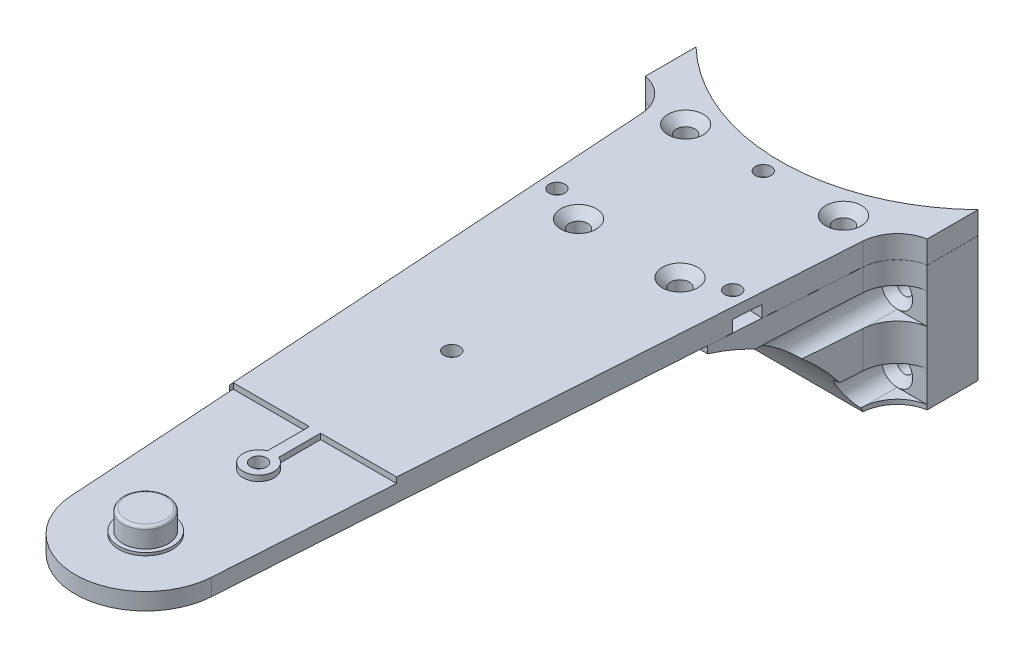
SolidWorks part; units mm, degrees
ref_plane "Front Plane" through (0, 0, 0) normal (0, 0, 1) x (1, 0, 0)
ref_plane "Top Plane" through (0, 0, 0) normal (0, 1, 0) x (1, 0, 0)
ref_plane "Right Plane" through (0, 0, 0) normal (1, 0, 0) x (0, 0, -1)
sketch "Sketch1" plane through (0, 0, 0) normal (0, 1, 0) x (1, 0, 0)
  line L0 (0, 0) -> (0, -148.5) construction
  line L1 (-22.202, -1.4609) -> (-12.473, -149.3207) construction
  line L2 (22.202, -1.4609) -> (12.473, -149.3207) construction
  line L3 (-12.473, -149.3207) -> (-19.6067, -40.9037)
  line L4 (12.473, -149.3207) -> (19.6067, -40.9037)
  line L5 (-25, -25.9037) -> (25, -25.9037) construction
  line L6 (-25, -25.9037) -> (-25, -34.9037)
  line L7 (25, -25.9037) -> (25, -34.9037)
  circle A0 centre (0, 0) radius 36 construction
  arc A1 (-12.473, -149.3207) -> (12.473, -149.3207) centre (0, -148.5) ccw
  circle A2 centre (0, 0) radius 19.5 construction
  circle A3 centre (0, 19.5) radius 2.75 construction
  circle A4 centre (0, 0) radius 22.25 construction
  arc A5 (-25, -25.9037) -> (25, -25.9037) centre (0, 0) ccw
  arc A6 (-25, -34.9037) -> (-19.6067, -40.9037) centre (-26.1174, -41.3321) cw
  arc A7 (25, -34.9037) -> (19.6067, -40.9037) centre (26.1174, -41.3321) ccw
  dimension "D1" = 72
  dimension "D3" = 25
  dimension "D4" = 39
  dimension "D5" = 5.5
  dimension "D2" = 148.5
  dimension "D6" = 50
  dimension "D7" = 9
  dimension "D8" = 15
extrude "Boss-Extrude1" add sketch "Sketch1" against normal blind 4
sketch "Sketch2" plane through (0, -4, 0) normal (0, -1, 0) x (1, 0, 0)
  line L0 (25, 34.9037) -> (25, 25.9037) construction
  line L1 (-25, 25.9037) -> (-25, 34.9037) construction
  line L2 (25, 34.9037) -> (25, 25.9037)
  line L3 (-25, 25.9037) -> (-25, 34.9037)
  line L4 (-19.6067, 40.9037) -> (19.6067, 40.9037)
  arc A0 (19.6067, 40.9037) -> (25, 34.9037) centre (26.1174, 41.3321) ccw construction
  arc A1 (25, 25.9037) -> (-25, 25.9037) centre (0, 0) ccw construction
  arc A2 (-25, 34.9037) -> (-19.6067, 40.9037) centre (-26.1174, 41.3321) ccw construction
  arc A3 (19.6067, 40.9037) -> (25, 34.9037) centre (26.1174, 41.3321) ccw
  arc A4 (25, 25.9037) -> (-25, 25.9037) centre (0, 0) ccw
  arc A5 (-25, 34.9037) -> (-19.6067, 40.9037) centre (-26.1174, 41.3321) ccw
extrude "Boss-Extrude2" add sketch "Sketch2" along normal offset from surface (22.2378 mm away) 26.2378 up to face at (0, 0, 65.2465)
ref_plane "Plane1" through (0, 0, 34.9037) normal (0, 0, 1) x (1, 0, 0)
fillet "Fillet2" radius 40 1 edges at (0, -4, 40.9037)
sketch "Sketch3" plane through (0, 0, 34.9037) normal (0, 0, 1) x (1, 0, 0)
  line L0 (25, 0) -> (-25, 0) construction
  line L1 (-19.6636, -22.6878) -> (19.6636, -22.6878) construction
  line L2 (-19.6636, -22.6878) -> (-19.6636, -10.6878) construction
  line L3 (-19.6636, -10.6878) -> (19.6636, -10.6878) construction
  line L4 (19.6636, -22.6878) -> (19.6636, -10.6878) construction
  line L5 (-19.6636, -22.6878) -> (19.6636, -10.6878) construction
  line L6 (-19.6636, -10.6878) -> (19.6636, -22.6878) construction
  line L7 (-19.6636, -7.9378) -> (-25, -7.9378)
  line L8 (-25, -7.9378) -> (-25, -13.4378)
  line L9 (-25, -13.4378) -> (-19.6636, -13.4378)
  line L10 (-25, -26.2378) -> (-25, 0) construction
  line L11 (0, -16.6878) -> (-25, -16.6878) construction
  line L12 (-25, -25.4378) -> (-25, -19.9378)
  line L13 (-25, -19.9378) -> (-19.6636, -19.9378)
  line L14 (-19.6636, -25.4378) -> (-25, -25.4378)
  line L15 (0, -16.6878) -> (0, 0) construction
  line L16 (19.6636, -25.4378) -> (25, -25.4378)
  line L17 (25, -19.9378) -> (19.6636, -19.9378)
  line L18 (25, -25.4378) -> (25, -19.9378)
  line L19 (25, -13.4378) -> (19.6636, -13.4378)
  line L20 (25, -7.9378) -> (25, -13.4378)
  line L21 (19.6636, -7.9378) -> (25, -7.9378)
  arc A0 (-19.6636, -13.4378) -> (-19.6636, -7.9378) centre (-19.6636, -10.6878) ccw
  arc A4 (-19.6636, -19.9378) -> (-19.6636, -25.4378) centre (-19.6636, -22.6878) cw
  arc A5 (19.6636, -19.9378) -> (19.6636, -25.4378) centre (19.6636, -22.6878) ccw
  arc A6 (19.6636, -13.4378) -> (19.6636, -7.9378) centre (19.6636, -10.6878) cw
  point P0 (0, -16.6878)
  dimension "D4" = 5.5
  dimension "D1" = 10.6878
  dimension "D2" = 12
  dimension "D3" = 39.3272
extrude "Cut-Extrude1" cut sketch "Sketch3" along normal through all
chamfer "Chamfer1" [suppressed] distance 2.75 angle 60
hole_wizard "CSK for M2.5 Flat Head Machine Screw1" positions "Sketch5" profile "Sketch6" countersink size "M2.5" standard "ANSI Metric" end condition through all
sketch "Sketch5" plane through (0, 0, 34.9037) normal (0, 0, 1) x (1, 0, 0)
  point P0 (19.6636, -22.6878)
  point P3 (-19.6636, -22.6878)
  point P6 (-19.6636, -10.6878)
  point P9 (19.6636, -10.6878)
sketch "Sketch6" plane through (19.6636, -22.6878, 34.9037) normal (1, 0, 0) x (0, -1, 0)
  line L0 (0, 0) -> (0, 9)
  line L1 (0, 9) -> (1.4, 9)
  line L2 (1.4, 9) -> (1.4, 1.35)
  line L3 (1.4, 1.35) -> (2.75, 0)
  line L5 (2.75, 0) -> (0, 0)
  line L6 (-1.4, 1.35) -> (-2.75, 0) construction
  line L11 (0, -6.35) -> (0, 107.95) construction
  dimension "Thru Hole Dia." = 2.8
  dimension "Thru Hole Depth" = 9
  dimension "Near C'Sink Dia." = 5.5
  dimension "Near C'Sink Angle" = 90
sketch "Sketch8" plane through (0, 0, 0) normal (0, 1, 0) x (1, 0, 0)
  line L9 (-3.9772, -124.3701) -> (-3.9783, -118.5007)
  line L10 (-3.9783, -118.5007) -> (-12.9545, -118.5024)
  line L11 (-12.9545, -118.5024) -> (-14.4578, -118.5026)
  line L12 (-14.4578, -118.5026) -> (-14.4468, -178.5026)
  line L13 (-14.4468, -178.5026) -> (14.5121, -178.4973)
  line L14 (14.5121, -178.4973) -> (14.5012, -118.4973)
  line L15 (14.5012, -118.4973) -> (12.9979, -118.4976)
  line L16 (12.9979, -118.4976) -> (4.0217, -118.4993)
  line L17 (4.0217, -118.4993) -> (4.0228, -124.3686)
  line L21 (-14.4578, -118.5026) -> (-14.4468, -178.5026)
  line L22 (-14.4468, -178.5026) -> (14.5121, -178.4973)
  line L23 (14.5121, -178.4973) -> (14.5012, -118.4973)
  line L27 (-0.9823, -96.8119) -> (-0.9769, -125.9384) construction
  line L28 (1.0177, -96.8116) -> (1.0231, -125.9381) construction
  line L29 (-0.9783, -118.5002) -> (-0.9769, -125.9384)
  line L30 (1.0217, -118.4998) -> (1.0231, -125.9381)
  line L31 (1.0217, -118.4998) -> (14.5012, -118.4973)
  line L72 (-14.4578, -118.5026) -> (-0.9783, -118.5002)
  arc A1 (-3.9772, -124.3701) -> (4.0228, -124.3686) centre (0.0235, -128.5) ccw
  arc A2 (-3.9772, -124.3701) -> (4.0228, -124.3686) centre (0.0235, -128.5) ccw construction
  arc A8 (-0.9769, -125.9384) -> (1.0231, -125.9381) centre (0.0235, -128.5) ccw
  dimension "D2" = 5.5
  dimension "D1" = 0
extrude "Cut-Extrude3" cut sketch "Sketch8" against normal blind 1
sketch "Sketch9" plane through (0, -4, 0) normal (0, -1, 0) x (1, 0, 0)
  line L0 (-17.2485, 76.7436) -> (17.2485, 76.7436)
  line L1 (17.2485, 76.7436) -> (17.9065, 66.7436)
  line L2 (17.9065, 66.7436) -> (-17.9065, 66.7436)
  line L3 (-17.9065, 66.7436) -> (-17.2485, 76.7436)
  line L4 (-17.2485, 76.7436) -> (-12.473, 149.3207) construction
  line L5 (12.473, 149.3207) -> (17.2485, 76.7436) construction
  dimension "D1" = 10
extrude "Cut-Extrude4" cut sketch "Sketch9" along normal through all
sketch "Sketch11" plane through (0, -4, 0) normal (0, -1, 0) x (1, 0, 0)
  circle A0 centre (0, 0) radius 161
extrude "Cut-Extrude5" cut sketch "Sketch11" along normal blind 0.01
sketch "Sketch12" plane through (0, 0, 0) normal (0, 1, 0) x (1, 0, 0)
  line L0 (-17.9065, -66.7436) -> (17.9065, -66.7436) construction
  line L1 (-17.9065, -66.7436) -> (17.9065, -66.7436) construction
  line L3 (-9, -62.7436) -> (9, -62.7436) construction
  line L4 (-9, -62.7436) -> (-14, -38.7436) construction
  line L5 (-14, -38.7436) -> (14, -38.7436) construction
  line L6 (9, -62.7436) -> (14, -38.7436) construction
  line L7 (-9, -62.7436) -> (14, -38.7436) construction
  line L8 (-14, -38.7436) -> (9, -62.7436) construction
  circle A0 centre (-14, -38.7436) radius 1.65
  circle A1 centre (14, -38.7436) radius 1.65
  circle A2 centre (-9, -62.7436) radius 1.65
  circle A3 centre (9, -62.7436) radius 1.65
  point P2 (0, -53.3523)
  point P15 (0, -62.7436)
  dimension "D1" = 3.3
  dimension "D2" = 4
  dimension "D3" = 28
  dimension "D4" = 24
  dimension "D5" = 18
extrude "Cut-Extrude6" cut sketch "Sketch12" against normal blind 8.25
ref_plane "Plane2" through (0, -5.2702, 0) normal (0, 1, 0) x (1, 0, 0)
sketch "Sketch13" plane through (0, -5.2702, 0) normal (0, 1, 0) x (1, 0, 0)
  line L0 (0, 0) -> (0, -36) construction
  line L1 (-11.75, -59.9936) -> (-6.25, -59.9936)
  line L2 (-11.75, -59.9936) -> (-11.75, -65.4936)
  line L3 (-11.75, -65.4936) -> (-6.25, -65.4936) construction
  line L4 (-6.25, -59.9936) -> (-6.25, -65.4936)
  line L5 (-11.75, -59.9936) -> (-6.25, -65.4936) construction
  line L6 (-11.75, -65.4936) -> (-6.25, -59.9936) construction
  line L7 (-6.25, -65.4936) -> (-6.25, -66.7436)
  line L8 (-17.9065, -66.7436) -> (17.9065, -66.7436) construction
  line L9 (-6.25, -66.7436) -> (-11.75, -66.7436)
  line L10 (-11.75, -66.7436) -> (-11.75, -65.4936)
  line L11 (6.25, -66.7436) -> (11.75, -66.7436)
  line L12 (6.25, -65.4936) -> (6.25, -66.7436)
  line L13 (6.25, -59.9936) -> (6.25, -65.4936)
  line L14 (11.75, -59.9936) -> (6.25, -59.9936)
  line L15 (11.75, -59.9936) -> (11.75, -65.4936)
  line L16 (11.75, -66.7436) -> (11.75, -65.4936)
  arc A0 (-25, -25.9037) -> (25, -25.9037) centre (0, 0) ccw construction
  point P0 (-9, -62.7436)
  dimension "D1" = 5.5
extrude "Cut-Extrude7" cut sketch "Sketch13" against normal blind 8.5
sketch "Sketch14" plane through (0, -8.25, 0) normal (0, 1, 0) x (1, 0, 0)
  line L0 (0, 0) -> (0, -36) construction
  line L1 (-14, -38.7436) -> (0, 0) construction
  line L2 (-15.6518, -35.2228) -> (-10.4791, -37.0919) construction
  line L3 (-15.6518, -35.2228) -> (-17.5209, -40.3954)
  line L4 (-17.5209, -40.3954) -> (-12.3482, -42.2645)
  line L5 (-10.4791, -37.0919) -> (-12.3482, -42.2645)
  line L6 (-15.6518, -35.2228) -> (-12.3482, -42.2645) construction
  line L7 (-17.5209, -40.3954) -> (-10.4791, -37.0919) construction
  line L8 (-15.6518, -35.2228) -> (-14.7849, -32.8239)
  line L9 (-14.7849, -32.8239) -> (-9.6123, -34.693)
  line L10 (-9.6123, -34.693) -> (-10.4791, -37.0919)
  line L11 (14.7849, -32.8239) -> (9.6123, -34.693)
  line L12 (15.6518, -35.2228) -> (14.7849, -32.8239)
  line L13 (15.6518, -35.2228) -> (17.5209, -40.3954)
  line L14 (17.5209, -40.3954) -> (12.3482, -42.2645)
  line L15 (10.4791, -37.0919) -> (12.3482, -42.2645)
  line L16 (9.6123, -34.693) -> (10.4791, -37.0919)
  arc A0 (-25, -25.9037) -> (25, -25.9037) centre (0, 0) ccw construction
  point P6 (-14, -38.7436)
  dimension "D1" = 5.5
extrude "Cut-Extrude8" cut sketch "Sketch14" along normal blind 2
hole_wizard "CSK for M3 Flat Head Machine Screw1" positions "Sketch15" profile "Sketch16" countersink size "M3" standard "ANSI Metric"
sketch "Sketch15" plane through (0, 0, 0) normal (0, 1, 0) x (1, 0, 0)
  point P0 (-14, -38.7436)
  point P3 (14, -38.7436)
  point P6 (9, -62.7436)
  point P9 (-9, -62.7436)
sketch "Sketch16" plane through (-14, 0, 38.7436) normal (1, 0, 0) x (0, 0, 1)
  line L0 (0, 0) -> (0, 8.9914)
  line L1 (0, 8.9914) -> (1.65, 8)
  line L2 (1.65, 8) -> (1.65, 1.5)
  line L3 (1.65, 1.5) -> (3.15, 0)
  line L5 (3.15, 0) -> (0, 0)
  line L6 (-1.65, 1.5) -> (-3.15, 0) construction
  line L10 (0, 8.9914) -> (-1.65, 8) construction
  line L11 (0, -6.35) -> (0, 107.95) construction
  dimension "Hole Dia." = 3.3
  dimension "Hole Depth" = 8
  dimension "Near C'Sink Dia." = 6.3
  dimension "Near C'Sink Angle" = 90
  dimension "Drill Angle" = 118
sketch "Sketch18" plane through (0, -4, 0) normal (0, -1, 0) x (1, 0, 0)
  circle A0 centre (0.0235, 128.5) radius 1.4
  circle A1 centre (0.0071, 39) radius 2.75
  circle A2 centre (0.0071, 39) radius 2.75 construction
  circle A3 centre (0.0173, 94.25) radius 2.75
  circle A4 centre (0.0173, 94.25) radius 2.75 construction
  circle A5 centre (0.0235, 128.5) radius 2.75
  circle A6 centre (0.0235, 128.5) radius 2.75 construction
  circle A7 centre (0.0173, 94.25) radius 1.4
  circle A9 centre (-15.5725, 60.0029) radius 1.4
  circle A11 centre (-15.5725, 60.0029) radius 2.75
  circle A12 centre (-15.5725, 60.0029) radius 2.75 construction
  circle A13 centre (15.5944, 59.9971) radius 1.4
  circle A15 centre (0.0071, 39) radius 1.4
  circle A17 centre (15.5944, 59.9971) radius 2.75
  circle A18 centre (15.5944, 59.9971) radius 2.75 construction
  dimension "D4" = 2.8
  dimension "D1" = 0
  dimension "D2" = 0
  dimension "D3" = 0
  dimension "D6" = 0
  dimension "D9" = 0
extrude "Cut-Extrude9" cut sketch "Sketch18" against normal through all
sketch "Sketch19" plane through (0, -4, 0) normal (0, -1, 0) x (1, 0, 0)
  line L1 (1.4525, 130.975) -> (-1.4054, 130.975)
  line L2 (-1.4054, 130.975) -> (-2.8344, 128.5)
  line L3 (-2.8344, 128.5) -> (-1.4054, 126.025)
  line L4 (-1.4054, 126.025) -> (1.4525, 126.025)
  line L5 (1.4525, 126.025) -> (2.8814, 128.5)
  line L6 (2.8814, 128.5) -> (1.4525, 130.975)
  line L7 (1.4462, 96.725) -> (-1.4117, 96.725)
  line L8 (-1.4117, 96.725) -> (-2.8406, 94.25)
  line L9 (-2.8406, 94.25) -> (-1.4117, 91.775)
  line L10 (-1.4117, 91.775) -> (1.4462, 91.775)
  line L11 (1.4462, 91.775) -> (2.8751, 94.25)
  line L12 (2.8751, 94.25) -> (1.4462, 96.725)
  line L13 (-12.7208, 59.8152) -> (-13.9841, 62.3787)
  line L14 (-13.9841, 62.3787) -> (-16.8358, 62.5663)
  line L15 (-16.8358, 62.5663) -> (-18.4242, 60.1905) construction
  line L16 (-18.4242, 60.1905) -> (-17.1608, 57.627) construction
  line L17 (-17.1608, 57.627) -> (-14.3091, 57.4394)
  line L18 (-14.3091, 57.4394) -> (-12.7208, 59.8152)
  line L19 (2.4786, 37.5649) -> (2.4857, 40.4228)
  line L20 (2.4857, 40.4228) -> (0.0143, 41.8579)
  line L21 (0.0143, 41.8579) -> (-2.4643, 40.4351)
  line L22 (-2.4643, 40.4351) -> (-2.4714, 37.5772)
  line L23 (-2.4714, 37.5772) -> (0, 36.1421) construction
  line L24 (0, 36.1421) -> (2.4786, 37.5649) construction
  line L25 (0, 0) -> (0, 161) construction
  line L26 (-18.4242, 60.1905) -> (-15.5725, 60.0029) construction
  line L27 (-19.6067, 40.9037) -> (-12.473, 149.3207) construction
  line L28 (-16.8358, 62.5663) -> (-18.1755, 62.6545)
  line L29 (-18.1755, 62.6545) -> (-18.5005, 57.7152)
  line L30 (-18.5005, 57.7152) -> (-17.1608, 57.627)
  line L31 (18.1755, 62.6545) -> (18.5005, 57.7152)
  line L32 (16.8358, 62.5663) -> (18.1755, 62.6545)
  line L33 (13.9841, 62.3787) -> (16.8358, 62.5663)
  line L34 (12.7208, 59.8152) -> (13.9841, 62.3787)
  line L35 (14.3091, 57.4394) -> (12.7208, 59.8152)
  line L36 (17.1608, 57.627) -> (14.3091, 57.4394)
  line L37 (18.5005, 57.7152) -> (17.1608, 57.627)
  line L38 (-2.4714, 37.5772) -> (-2.4714, 35.9151)
  line L39 (-2.4714, 35.9151) -> (2.4786, 35.9146)
  line L40 (2.4786, 35.9146) -> (2.4786, 37.5649)
  circle A0 centre (0.0235, 128.5) radius 2.475 construction
  circle A1 centre (0.0173, 94.25) radius 2.475 construction
  circle A2 centre (-15.5725, 60.0029) radius 2.475 construction
  circle A3 centre (0.0071, 39) radius 2.475 construction
  arc A4 (12.473, 149.3207) -> (-12.473, 149.3207) centre (0, 148.5) ccw construction
  arc A5 (25, 25.9037) -> (-25, 25.9037) centre (0, 0) ccw construction
  dimension "D1" = 4.95
extrude "Cut-Extrude10" cut sketch "Sketch19" against normal blind 2.1
sketch "Sketch20" plane through (0, -1, 0) normal (0, 1, 0) x (1, 0, 0)
  circle A0 centre (0, -148.5) radius 4.75
  dimension "D1" = 9.5
extrude "Boss-Extrude3" add sketch "Sketch20" along normal blind 0.5
sketch "Sketch21" plane through (0, -0.5, 0) normal (0, 1, 0) x (1, 0, 0)
  circle A0 centre (0, -148.5) radius 4
  dimension "D1" = 8
extrude "Boss-Extrude4" add sketch "Sketch21" along normal blind 3.5
fillet "Fillet4" radius 0.5 1 edges at (0, 3, 152.5)
